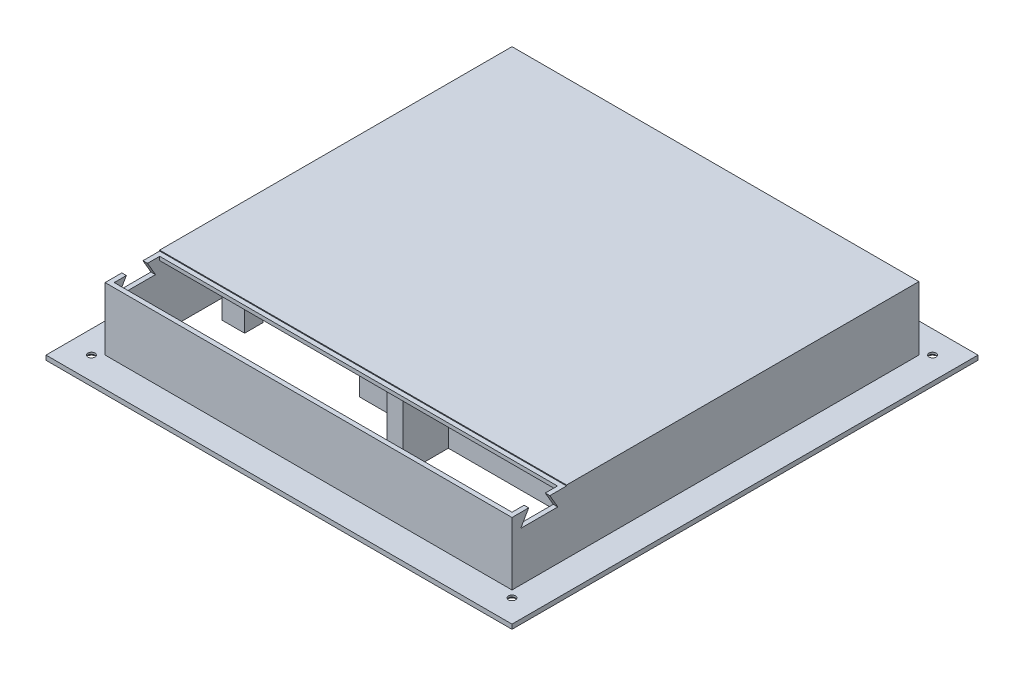
SolidWorks part; units mm, degrees
ref_plane "Front Plane" through (0, 0, 0) normal (0, 0, 1) x (1, 0, 0)
ref_plane "Top Plane" through (0, 0, 0) normal (0, 1, 0) x (1, 0, 0)
ref_plane "Right Plane" through (0, 0, 0) normal (1, 0, 0) x (0, 0, -1)
sketch "Sketch1" plane through (0, 0, 0) normal (0, 1, 0) x (1, 0, 0)
  line L1 (-87.5, 87.5) -> (87.5, 87.5)
  line L2 (-87.5, 87.5) -> (-87.5, -87.5)
  line L3 (-87.5, -87.5) -> (87.5, -87.5)
  line L4 (87.5, 87.5) -> (87.5, -87.5)
  line L5 (-87.5, 87.5) -> (87.5, -87.5) construction
  line L6 (-87.5, -87.5) -> (87.5, 87.5) construction
  point P0 (0, 0)
  dimension "D1" = 175
  dimension "D2" = 175
extrude "Boss-Extrude1" add sketch "Sketch1" along normal blind 2
sketch "Sketch2" plane through (0, 0, 0) normal (0, 1, 0) x (1, 0, 0)
  line L4 (-83, -33.5) -> (-79.25, -33.5)
  line L5 (-71.125, -48.5) -> (-61.125, -48.5)
  line L6 (-82.5, 42.5) -> (-78.75, 42.5)
  line L7 (-82.5, 42.5) -> (-82.5, 30.5)
  line L8 (-82.5, 30.5) -> (-78.75, 30.5)
  line L9 (-78.75, 42.5) -> (-78.75, 30.5)
  line L10 (-82.5, 42.5) -> (-78.75, 30.5) construction
  line L11 (-82.5, 30.5) -> (-78.75, 42.5) construction
  line L12 (87.5, 87.5) -> (-87.5, 87.5) construction
  line L13 (-87.5, 87.5) -> (-87.5, -87.5) construction
  line L14 (-48.7483, 30.5) -> (-52.4983, 30.5)
  line L15 (-48.7483, 42.5) -> (-48.7483, 30.5)
  line L16 (-52.4983, 42.5) -> (-52.4983, 30.5)
  line L17 (-48.7483, 42.5) -> (-52.4983, 42.5)
  line L18 (-44.5, 49) -> (-40.75, 49)
  line L19 (-83, -33.5) -> (-83, -45.5)
  line L20 (-83, -45.5) -> (-79.25, -45.5)
  line L21 (-79.25, -33.5) -> (-79.25, -45.5)
  line L22 (-83, -33.5) -> (-79.25, -45.5) construction
  line L23 (-83, -45.5) -> (-79.25, -33.5) construction
  line L28 (-87.5, -87.5) -> (87.5, -87.5) construction
  line L29 (-53, -33.5) -> (-49.25, -33.5)
  line L30 (-53, -33.5) -> (-53, -45.5)
  line L31 (-53, -45.5) -> (-49.25, -45.5)
  line L32 (-49.25, -33.5) -> (-49.25, -45.5)
  line L33 (-53, -33.5) -> (-49.25, -45.5) construction
  line L34 (-53, -45.5) -> (-49.25, -33.5) construction
  line L35 (-44.5, 49) -> (-44.5, 37)
  line L36 (-44.5, 37) -> (-40.75, 37)
  line L37 (-40.75, 49) -> (-40.75, 37)
  line L38 (-44.5, 49) -> (-40.75, 37) construction
  line L39 (-44.5, 37) -> (-40.75, 49) construction
  line L40 (-14.5, 49) -> (-10.75, 49)
  line L41 (-14.5, 49) -> (-14.5, 37)
  line L42 (-14.5, 37) -> (-10.75, 37)
  line L43 (-10.75, 49) -> (-10.75, 37)
  line L44 (-14.5, 49) -> (-10.75, 37) construction
  line L45 (-14.5, 37) -> (-10.75, 49) construction
  line L46 (-70.6242, 5.5249) -> (-60.6242, 5.5249)
  line L47 (-70.6242, 75.5249) -> (-60.6242, 75.5249)
  line L48 (-70.6242, 75.5249) -> (-70.6242, 67.5249)
  line L49 (-70.6242, 67.5249) -> (-60.6242, 67.5249)
  line L50 (-60.6242, 75.5249) -> (-60.6242, 67.5249)
  line L51 (-70.6242, 75.5249) -> (-60.6242, 67.5249) construction
  line L52 (-70.6242, 67.5249) -> (-60.6242, 75.5249) construction
  line L53 (-70.6242, 5.5249) -> (-70.6242, -2.4751)
  line L54 (-70.6242, -2.4751) -> (-60.6242, -2.4751)
  line L55 (-60.6242, 5.5249) -> (-60.6242, -2.4751)
  line L56 (-70.6242, 5.5249) -> (-60.6242, -2.4751) construction
  line L57 (-70.6242, -2.4751) -> (-60.6242, 5.5249) construction
  line L58 (-71.125, -20.5) -> (-61.125, -20.5)
  line L59 (-71.125, -20.5) -> (-71.125, -28.5)
  line L60 (-71.125, -28.5) -> (-61.125, -28.5)
  line L61 (-61.125, -20.5) -> (-61.125, -28.5)
  line L62 (-71.125, -20.5) -> (-61.125, -28.5) construction
  line L63 (-71.125, -28.5) -> (-61.125, -20.5) construction
  line L64 (-71.125, -48.5) -> (-71.125, -56.5)
  line L65 (-71.125, -56.5) -> (-61.125, -56.5)
  line L66 (-61.125, -48.5) -> (-61.125, -56.5)
  line L67 (-71.125, -48.5) -> (-61.125, -56.5) construction
  line L68 (-71.125, -56.5) -> (-61.125, -48.5) construction
  line L69 (-32.625, 6.5) -> (-22.625, 6.5)
  line L70 (-32.625, 76.5) -> (-22.625, 76.5)
  line L71 (-32.625, 76.5) -> (-32.625, 68.5)
  line L72 (-32.625, 68.5) -> (-22.625, 68.5)
  line L73 (-22.625, 76.5) -> (-22.625, 68.5)
  line L74 (-32.625, 76.5) -> (-22.625, 68.5) construction
  line L75 (-32.625, 68.5) -> (-22.625, 76.5) construction
  line L76 (-32.625, 6.5) -> (-32.625, -1.5)
  line L77 (-32.625, -1.5) -> (-22.625, -1.5)
  line L78 (-22.625, 6.5) -> (-22.625, -1.5)
  line L79 (-32.625, 6.5) -> (-22.625, -1.5) construction
  line L80 (-32.625, -1.5) -> (-22.625, 6.5) construction
  line L87 (4.5, 59.625) -> (12.5, 59.625)
  line L91 (4.5, 59.625) -> (4.5, 49.625)
  line L92 (4.5, 49.625) -> (12.5, 49.625)
  line L93 (12.5, 59.625) -> (12.5, 49.625)
  line L94 (4.5, 59.625) -> (12.5, 49.625) construction
  line L95 (4.5, 49.625) -> (12.5, 59.625) construction
  line L99 (87.5, -87.5) -> (87.5, 87.5) construction
  line L100 (57.5, 59.625) -> (65.5, 59.625)
  line L101 (57.5, 59.625) -> (57.5, 49.625)
  line L106 (57.5, 49.625) -> (65.5, 49.625)
  line L107 (65.5, 59.625) -> (65.5, 49.625)
  line L112 (57.5, 59.625) -> (65.5, 49.625) construction
  line L113 (57.5, 49.625) -> (65.5, 59.625) construction
  line L114 (32.5, 71.5) -> (44.5, 71.5)
  line L115 (32.5, 51.25) -> (44.5, 51.25)
  line L120 (32.5, 71.5) -> (32.5, 67.75)
  line L121 (32.5, 67.75) -> (44.5, 67.75)
  line L122 (32.5, 51.25) -> (32.5, 47.5)
  line L123 (32.5, 47.5) -> (44.5, 47.5)
  line L124 (44.5, 51.25) -> (44.5, 47.5)
  line L125 (32.5, 51.25) -> (44.5, 47.5) construction
  line L126 (32.5, 47.5) -> (44.5, 51.25) construction
  line L127 (44.5, 71.5) -> (44.5, 67.75)
  line L128 (32.5, 71.5) -> (44.5, 67.75) construction
  line L129 (32.5, 67.75) -> (44.5, 71.5) construction
  point P0 (-80.625, 36.5)
  point P5 (-52.4983, 36.5)
  point P6 (-78.75, 36.5)
  point P7 (-80.625, 42.5)
  point P16 (-81.125, -39.5)
  point P17 (-42.625, 43)
  point P19 (-53, -39.5)
  point P25 (8.5, 54.625)
  point P30 (-79.25, -39.5)
  point P31 (-65.6242, 1.5249)
  point P33 (-14.5, 43)
  point P38 (-65.6242, 71.5249)
  point P43 (-40.75, 43)
  point P51 (-27.625, 2.5)
  point P53 (-27.625, 72.5)
  point P55 (-66.125, -24.5)
  point P56 (-66.125, -52.5)
  point P75 (61.5, 54.625)
  point P80 (38.5, 49.375)
  point P85 (38.5, 69.625)
  dimension "D1" = 3.75
  dimension "D2" = 12
  dimension "D3" = 45
  dimension "D4" = 5
  dimension "D5" = 26.2517
  dimension "D6" = 3.75
  dimension "D7" = 12
  dimension "D8" = 3.75
  dimension "D9" = 12
  dimension "D10" = 4.5
  dimension "D11" = 42
  dimension "D12" = 26.25
  dimension "D13" = 26.25
  dimension "D14" = 43
  dimension "D15" = 11
  dimension "D16" = 10
  dimension "D17" = 8
  dimension "D18" = 8.1258
  dimension "D19" = 25.0249
  dimension "D20" = 62
  dimension "D21" = 8
  dimension "D22" = 20
  dimension "D23" = 10
  dimension "D24" = 8.125
  dimension "D25" = 5
  dimension "D26" = 10
  dimension "D27" = 8
  dimension "D28" = 62
  dimension "D29" = 19.5
  dimension "D30" = 8.125
  dimension "D31" = 10
  dimension "D32" = 8
  dimension "D33" = 10
  dimension "D34" = 8
  dimension "D35" = 43
  dimension "D36" = 20
  dimension "D37" = 40
  dimension "D38" = 45
  dimension "D39" = 8.125
  dimension "D40" = 3.75
  dimension "D41" = 12
  dimension "D42" = 16.5
  dimension "D43" = 3.75
  dimension "D44" = 12
extrude "Boss-Extrude13" add sketch "Sketch2" against normal blind 23 contours L87 L93 L92 L91 | L115 L124 L123 L122 | L114 L127 L121 L120 | L100 L107 L106 L101 region at (8.5, 0, -54.625) region at (38.5, 0, -49.375)
extrude "Boss-Extrude14" add sketch "Sketch2<4>" against normal blind 20 contours L5 L66 L65 L64 | L4 L21 L20 L19 | L29 L32 L31 L30 | L58 L61 L60 L59 region at (-81.125, 0, 39.5) region at (-66.125, 0, 52.5) region at (-51.125, 0, 39.5)
sketch "Sketch2<4>" plane through (0, 0, 0) normal (0, 1, 0) x (1, 0, 0) same geometry as "Sketch2"
extrude "Boss-Extrude15" add sketch "Sketch2<5>" against normal blind 22 contours L69 L78 L77 L76 | L35 L36 L37 L18 | L70 L73 L72 L71 | L40 L43 L42 L41 region at (-27.625, 0, -2.5)
sketch "Sketch2<5>" plane through (0, 0, 0) normal (0, 1, 0) x (1, 0, 0) same geometry as "Sketch2"
extrude "Boss-Extrude19" add sketch "Sketch2<7>" against normal blind 22 contours L46 L55 L54 L53 | L17 L15 L14 L16 | L7 L8 L9 L6 | L47 L50 L49 L48 region at (-50.6233, 0, -36.5) region at (-65.6242, 0, -1.5249)
sketch "Sketch2<7>" plane through (0, 0, 0) normal (0, 1, 0) x (1, 0, 0) same geometry as "Sketch2"
extrude "Boss-Extrude20" add sketch "Sketch2<8>" against normal blind 5 contours L70 L73 L72 L71 | L40 L43 L42 L41 | L18 L37 L36 L35 | L78 L77 L76 L69
sketch "Sketch2<8>" plane through (0, 0, 0) normal (0, 1, 0) x (1, 0, 0) same geometry as "Sketch2"
sketch "Sketch11" plane through (0, 0, 0) normal (0, -1, 0) x (1, 0, 0)
  line L0 (19.5, -10.5) -> (-0.5, -10.5)
  line L1 (79.5, -10.5) -> (24.5, -10.5)
  line L2 (79.5, -10.5) -> (79.5, -5.5)
  line L3 (79.5, -5.5) -> (24.5, -5.5)
  line L4 (-0.5, -10.5) -> (-0.5, -5.5)
  line L5 (24.5, -30.5) -> (19.5, -30.5)
  line L6 (24.5, -30.5) -> (24.5, -10.5)
  line L7 (24.5, 1.5) -> (19.5, 1.5)
  line L8 (19.5, -30.5) -> (19.5, -10.5)
  line L9 (19.5, -5.5) -> (19.5, 1.5)
  line L10 (19.5, -5.5) -> (-0.5, -5.5)
  line L12 (87.5, 87.5) -> (87.5, -87.5) construction
  line L13 (87.5, -87.5) -> (-87.5, -87.5) construction
  line L14 (24.5, -5.5) -> (24.5, 1.5)
  dimension "D1" = 5
  dimension "D2" = 5
  dimension "D3" = 8
  dimension "D4" = 57
  dimension "D6" = 20
  dimension "D7" = 55
extrude "Boss-Extrude7" add sketch "Sketch11" along normal blind 33
sketch "Sketch10" plane through (0, 0, 0) normal (0, -1, 0) x (1, 0, 0)
  line L0 (10.5, 35.5) -> (-21.5, 35.5)
  line L1 (72.5, 35.5) -> (17.5, 35.5)
  line L2 (72.5, 35.5) -> (72.5, 45.5)
  line L3 (72.5, 45.5) -> (17.5, 45.5)
  line L4 (-21.5, 35.5) -> (-21.5, 45.5)
  line L5 (17.5, 12.5) -> (10.5, 12.5)
  line L6 (17.5, 12.5) -> (17.5, 35.5)
  line L7 (17.5, 65.5) -> (10.5, 65.5)
  line L8 (10.5, 12.5) -> (10.5, 35.5)
  line L9 (17.5, 45.5) -> (17.5, 65.5)
  line L10 (10.5, 45.5) -> (10.5, 65.5)
  line L11 (10.5, 45.5) -> (-21.5, 45.5)
  line L12 (87.5, 87.5) -> (87.5, -87.5) construction
  line L13 (87.5, -87.5) -> (-87.5, -87.5) construction
  dimension "D1" = 7
  dimension "D2" = 10
  dimension "D3" = 100
  dimension "D4" = 20
  dimension "D6" = 55
  dimension "D7" = 15
  dimension "D8" = 23
extrude "Boss-Extrude6" add sketch "Sketch10" along normal blind 30
sketch "Sketch4" plane through (0, 2, 0) normal (0, -1, 0) x (1, 0, 0)
  line L0 (-87.5, 87.5) -> (87.5, 87.5) construction
  line L1 (-89.5, 89.5) -> (89.5, 89.5)
  line L3 (-87.5, 87.5) -> (87.5, 87.5)
  line L6 (89.5, 89.5) -> (89.5, -89.5)
  line L8 (87.5, 87.5) -> (87.5, -87.5)
  line L10 (-89.5, 89.5) -> (-89.5, -89.5)
  line L12 (-87.5, 87.5) -> (-87.5, -87.5)
  line L13 (-89.5, -89.5) -> (89.5, -89.5)
  line L15 (-87.5, -87.5) -> (87.5, -87.5)
  line L17 (87.5, 87.5) -> (87.5, -87.5) construction
  line L21 (-87.5, -87.5) -> (-87.5, 87.5) construction
  line L22 (87.5, -87.5) -> (-87.5, -87.5) construction
  dimension "D2" = 2
  dimension "D3" = 2
  dimension "D5" = 2
  dimension "D6" = 2
extrude "Boss-Extrude3" add sketch "Sketch4" along normal blind 30
sketch "Sketch5" plane through (0, -28, 0) normal (0, -1, 0) x (1, 0, 0)
  line L1 (-102.5, 102.5) -> (102.5, 102.5)
  line L2 (-102.5, 102.5) -> (-102.5, -102.5)
  line L3 (-102.5, -102.5) -> (102.5, -102.5)
  line L4 (102.5, 102.5) -> (102.5, -102.5)
  line L5 (-102.5, 102.5) -> (102.5, -102.5) construction
  line L6 (-102.5, -102.5) -> (102.5, 102.5) construction
  line L7 (-89.5, 89.5) -> (89.5, 89.5)
  line L8 (-89.5, 89.5) -> (-89.5, -89.5)
  line L9 (-89.5, -89.5) -> (89.5, -89.5)
  line L10 (89.5, 89.5) -> (89.5, -89.5)
  line L11 (-89.5, 89.5) -> (89.5, -89.5) construction
  line L12 (-89.5, -89.5) -> (89.5, 89.5) construction
  point P0 (0, 0)
  point P6 (0, 0)
  dimension "D1" = 205
  dimension "D2" = 205
sketch "Sketch15" plane through (0, 2, 0) normal (0, 1, 0) x (1, 0, 0)
  line L0 (89.5, 89.5) -> (89.5, -89.5) construction
  line L1 (-89.5, -89.5) -> (89.5, -89.5)
  line L2 (-89.5, -89.5) -> (-89.5, -87.5)
  line L3 (-89.5, -87.5) -> (89.5, -87.5)
  line L4 (89.5, -89.5) -> (89.5, -87.5)
  dimension "D1" = 2
extrude "Boss-Extrude9" add sketch "Sketch15" along normal blind 90
sketch "Sketch13" plane through (0, 0, 0) normal (0, -1, 0) x (1, 0, 0)
  line L5 (87.5, 87.5) -> (87.5, -87.5) construction
  line L16 (-87.5, 87.5) -> (87.5, 87.5)
  line L17 (-87.5, 87.5) -> (-87.5, 67.5)
  line L18 (-87.5, 67.5) -> (87.5, 67.5)
  line L19 (87.5, 87.5) -> (87.5, 67.5)
  dimension "D1" = 20
extrude "Cut-Extrude2" cut sketch "Sketch13" against normal up to surface (2 mm away) up to face at (0, 2, -1)
sketch "Sketch17" plane through (0, 0, 87.5) normal (0, 0, -1) x (-1, 0, 0)
  line L12 (0.5, 35) -> (15.5, 35)
  line L14 (15.5, 50) -> (20.5, 50)
  line L16 (20.5, 30) -> (0.5, 30)
  line L17 (0.5, 30) -> (0.5, 35)
  line L19 (-87.5, 35) -> (-62.5, 35)
  line L20 (-62.5, 35) -> (-62.5, 30)
  line L21 (-62.5, 30) -> (-87.5, 30)
  line L22 (-87.5, 30) -> (-87.5, 35)
  line L24 (15.5, 50) -> (15.5, 35)
  line L25 (-89.5, 92) -> (-89.5, 2) construction
  line L29 (13.5, 77.3) -> (18.5, 77.3)
  line L30 (13.5, 77.3) -> (13.5, 90)
  line L31 (13.5, 90) -> (18.5, 90)
  line L32 (18.5, 77.3) -> (18.5, 90)
  line L33 (56.5, 35) -> (56.5, 15)
  line L34 (56.5, 35) -> (20.5, 35)
  line L36 (51.5, 30) -> (20.5, 30)
  line L38 (56.5, 15) -> (87.5, 15)
  line L39 (87.5, 15) -> (87.5, 10)
  line L40 (87.5, 10) -> (51.5, 10)
  line L41 (51.5, 10) -> (51.5, 30)
  line L43 (20.5, 35) -> (20.5, 50)
  line L45 (-89.5, 92) -> (89.5, 92) construction
  line L46 (89.5, 92) -> (89.5, 2) construction
  point P6 (-62.5, 32.5)
  point P26 (0.5, 32.5)
  dimension "D3" = 5
  dimension "D4" = 20
  dimension "D5" = 5
  dimension "D6" = 20
  dimension "D7" = 5
  dimension "D8" = 12.7
  dimension "D10" = 2
  dimension "D11" = 15
  dimension "D12" = 5
  dimension "D13" = 25
  dimension "D14" = 31
  dimension "D15" = 2
  dimension "D16" = 2
  dimension "D17" = 2
  dimension "D18" = 5
  dimension "D19" = 36
  dimension "D20" = 63
  dimension "D21" = 5
  dimension "D22" = 20
  dimension "D23" = 20
  dimension "D24" = 27.3
extrude "Boss-Extrude11" add sketch "Sketch17" along normal blind 5 contours L22 L21 L20 L19 | L16 L43 L14 L24 L12 L17 | L29 L32 L31 L30 | L34 L43 L14 L24 L12 L17 L16 L36 L41 L40 L39 L38 L33 region at (-8, 34.0425, 87.5) region at (75, 32.5, 87.5) region at (-16, 83.65, 87.5)
ref_plane "Plane1" through (87.5, 2, 87.5) normal (0, 0, 1) x (1, 0, 0)
sketch "Sketch24" plane through (89.5, 0, 0) normal (1, 0, 0) x (0, 0, -1)
  line L0 (-65.5, 2) -> (-65.5, 30.4086)
  line L1 (89.5, 2) -> (-87.5, 2) construction
  line L2 (-65.5, 30.4086) -> (-62.5, 33.4086)
  line L3 (-62.5, 33.4086) -> (-62.5, 92)
  line L4 (-62.5, 92) -> (-87.5, 92)
  line L5 (-87.5, 92) -> (-87.5, 2) construction
  line L6 (-87.5, 92) -> (-87.5, 2)
  line L7 (-87.5, 2) -> (-65.5, 2)
  dimension "D1" = 225
  dimension "D2" = 22
  dimension "D3" = 25
  dimension "D4" = 58.5914
extrude "Boss-Extrude16" add sketch "Sketch24" against normal blind 2 separate body
sketch "Sketch26" plane through (-89.5, 0, 0) normal (-1, 0, 0) x (0, 0, 1)
  line L0 (65.5, 2) -> (65.5, 30.4086)
  line L1 (65.5, 30.4086) -> (62.5, 33.4086)
  line L2 (62.5, 33.4086) -> (62.5, 92)
  line L3 (62.5, 92) -> (87.5, 92)
  line L4 (87.5, 92) -> (87.5, 2)
  line L5 (87.5, 2) -> (65.5, 2)
extrude "Boss-Extrude17" add sketch "Sketch26" against normal blind 2
sketch "Sketch27" plane through (-87.5, 0, 0) normal (1, 0, 0) x (0, 0, -1)
  line L0 (-64.5, 34.237) -> (-67.5, 31.237)
  line L1 (-62.5, 92) -> (-64.5, 92)
  line L2 (-62.5, 92) -> (-62.5, 33.4086)
  line L4 (-64.5, 92) -> (-64.5, 34.237)
  line L5 (-67.5, 31.237) -> (-67.5, 2)
  line L6 (-67.5, 2) -> (-65.5, 2)
  line L7 (-65.5, 2) -> (-65.5, 30.4086)
  line L8 (-65.5, 30.4086) -> (-62.5, 33.4086)
  line L9 (-87.5, 2) -> (-65.5, 2) construction
  line L10 (-65.5, 30.4086) -> (-65.5, 2) construction
  dimension "D1" = 2
  dimension "D2" = 2
  dimension "D3" = 2
extrude "Boss-Extrude18" add sketch "Sketch27" along normal up to next
extrude "Boss-Extrude4" add sketch "Sketch5" against normal blind 2
sketch "Sketch8" plane through (0, -28, 0) normal (0, -1, 0) x (-1, 0, 0)
  line L0 (102.5, 102.5) -> (-102.5, 102.5) construction
  line L1 (-102.5, 102.5) -> (-102.5, -102.5) construction
  line L2 (102.5, -102.5) -> (102.5, 102.5) construction
  line L3 (-102.5, -102.5) -> (102.5, -102.5) construction
  point P0 (-92.5, 92.5)
  point P2 (92.5, 92.5)
  point P4 (92.5, -92.5)
  point P6 (-92.5, -92.5)
  dimension "D1" = 10
  dimension "D2" = 10
  dimension "D3" = 10
  dimension "D4" = 10
  dimension "D5" = 10
  dimension "D6" = 10
  dimension "D7" = 10
  dimension "D8" = 10
hole_wizard "CSK for M2.5 Flat Head Machine Screw1" positions "Sketch8" profile "Sketch7" countersink size "M2.5" standard "ANSI Metric" end condition up to next
sketch "Sketch7" plane through (92.5, -28, -92.5) normal (1, 0, 0) x (0, 0, -1)
  line L0 (0, 0) -> (0, 2)
  line L1 (0, 2) -> (1.55, 2)
  line L2 (1.55, 2) -> (1.55, 1.2)
  line L3 (1.55, 1.2) -> (2.75, 0)
  line L5 (2.75, 0) -> (0, 0)
  line L6 (-1.55, 1.2) -> (-2.75, 0) construction
  line L11 (0, -6.35) -> (0, 107.95) construction
  dimension "Thru Hole Dia." = 3.1
  dimension "Thru Hole Depth" = 2
  dimension "Near C'Sink Dia." = 5.5
  dimension "Near C'Sink Angle" = 90
sketch "Sketch21" plane through (0, 92, 0) normal (0, 1, 0) x (1, 0, 0)
  line L21 (89.5, -89.5) -> (89.5, -62.5) construction
  line L25 (-89.5, -89.5) -> (89.5, -89.5)
  line L26 (-89.5, -89.5) -> (-89.5, -85.5)
  line L27 (-87.5, -85.5) -> (87.5, -85.5)
  line L28 (89.5, -89.5) -> (89.5, -85.5)
  line L29 (-89.5, -62.5) -> (-89.5, -89.5) construction
  line L31 (89.5, -62.5) -> (-89.5, -62.5)
  line L32 (89.5, -62.5) -> (89.5, -69.5)
  line L33 (87.5, -66.5) -> (-87.5, -66.5)
  line L34 (-89.5, -62.5) -> (-89.5, -66.5)
  line L36 (-89.5, -85.5) -> (-89.5, -66.5)
  line L38 (-87.5, -85.5) -> (-87.5, -66.5)
  line L41 (89.5, -85.5) -> (89.5, -69.5)
  line L43 (87.5, -85.5) -> (87.5, -66.5)
  line L44 (-89.5, -62.5) -> (89.5, -62.5) construction
  dimension "D1" = 4
  dimension "D2" = 4
extrude "Boss-Extrude12" add sketch "Sketch21" along normal blind 2 contours L28 L25 L26 L36 L34 L31 L32 L41 | L27 L43 L33 L38
sketch "Sketch22" plane through (89.5, 0, 0) normal (1, 0, 0) x (0, 0, -1)
  line L0 (-89.5, -26) -> (-89.5, 94) construction
  line L1 (-71.75, 82) -> (-86.75, 82)
  line L2 (-71.75, 82) -> (-71.75, 37)
  line L3 (-71.75, 37) -> (-86.75, 37)
  line L4 (-86.75, 82) -> (-86.75, 37)
  line L6 (-89.5, 94) -> (-62.5, 94) construction
  dimension "D1" = 2.75
  dimension "D2" = 45
  dimension "D3" = 12
  dimension "D4" = 15
extrude "Cut-Extrude3" cut sketch "Sketch22" against normal up to next
sketch "Sketch28" plane through (89.5, 0, 0) normal (1, 0, 0) x (0, 0, -1)
  line L0 (-65.5, 2) -> (-73.5, 2)
  line L1 (-65.5, 2) -> (-65.5, 30.4086) construction
  line L2 (89.5, 2) -> (-65.5, 2) construction
  line L3 (-73.5, 2) -> (-70, -4.0622)
  line L4 (-70, -4.0622) -> (-85, -4.0622)
  line L5 (-85, -4.0622) -> (-81.5, 2)
  line L6 (-81.5, 2) -> (-89.5, 2)
  line L7 (-89.5, -26) -> (-89.5, 94) construction
  point P6 (-77.5, -4.0622)
  dimension "D1" = 60
  dimension "D2" = 60
  dimension "D3" = 12
  dimension "D4" = 15
  dimension "D5" = 8
  dimension "D6" = 8
extrude "Cut-Extrude-Thin1" cut sketch "Sketch28" against normal through all thin thin type mid plane wall 0.75
chamfer "Chamfer1" distance 5 angle 45 rebuild error yes
chamfer "Chamfer2" distance 5 angle 45 rebuild error yes
chamfer "Chamfer3" distance 5 angle 45 rebuild error yes
chamfer "Chamfer4" distance 2 angle 45 rebuild error yes
sketch "Sketch29" plane through (0, 0, 62.5) normal (0, 0, -1) x (-1, 0, 0)
  line L0 (89.5, 2) -> (-89.5, 2) construction
  line L1 (-87.5, 94) -> (87.5, 94)
  line L2 (-87.5, 94) -> (-87.5, 2)
  line L3 (-87.5, 2) -> (87.5, 2)
  line L4 (87.5, 94) -> (87.5, 2)
  line L5 (87.5, 1.625) -> (87.5, 0) construction
  line L6 (-87.5, 1.625) -> (-87.5, 0) construction
  point P9 (0, 0)
extrude "Cut-Extrude4" cut sketch "Sketch29" against normal up to surface (5 mm away) rebuild error yes up to face at (0, 0.8125, 67.5)
